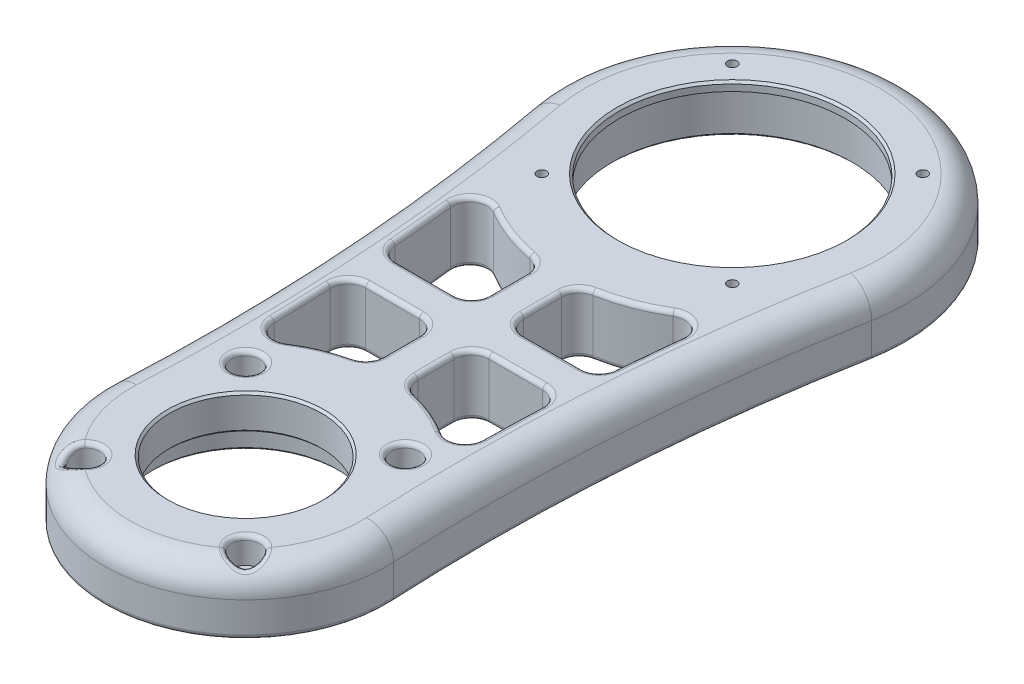
SolidWorks part; units mm, degrees
ref_plane "Front" through (0, 0, 0) normal (0, 0, 1) x (1, 0, 0)
ref_plane "Top" through (0, 0, 0) normal (0, 1, 0) x (1, 0, 0)
ref_plane "Right" through (0, 0, 0) normal (1, 0, 0) x (0, 0, -1)
sketch "Эскиз1" plane through (0, 0, 0) normal (0, 1, 0) x (1, 0, 0)
  line L0 (0, 0) -> (0, 112) construction
  line L3 (0, 0) -> (0, -109) construction
  circle A0 centre (0, 112) radius 40
  circle A1 centre (0, 0) radius 32.5
  circle A2 centre (0, -109) radius 50
  arc A3 (-48.1763, -95.6191) -> (-39.3342, 104.7321) centre (-477.8164, 23.7129) ccw
  arc A4 (39.3342, 104.7321) -> (48.1763, -95.6191) centre (477.8164, 23.7129) ccw
  dimension "D2" = 80
  dimension "D3" = 65
  dimension "D5" = 100
  dimension "D1" = 112
  dimension "D4" = 109
extrude "Бобышка-Вытянуть1" add sketch "Эскиз1" along normal blind 14 contours A2 A1 | A1 A0 | A0 region at (0, 0, -112) region at (0, 0, -52.811) region at (0, 0, 0)
sketch "Эскиз2" plane through (0, 0, 0) normal (0, 1, 0) x (1, 0, 0)
  circle A0 centre (0, 0) radius 21.1
  dimension "D1" = 42.2
extrude "Вырез-Вытянуть2" cut sketch "Эскиз2" along normal blind 6
sketch "Эскиз3" plane through (0, 0, 0) normal (0, 1, 0) x (1, 0, 0)
  circle A0 centre (0, 0) radius 17.5
  dimension "D1" = 35
extrude "Вырез-Вытянуть4" cut sketch "Эскиз3" along normal through all
sketch "Эскиз4" plane through (0, 0, 0) normal (0, 1, 0) x (1, 0, 0)
  line L0 (0, 0) -> (0, 65.2467) construction
  line L1 (0, 0) -> (-110.2485, 0) construction
  line L2 (0, 0) -> (18.3848, 18.3848) construction
  circle A0 centre (0, 0) radius 26 construction
  circle A1 centre (18.3848, 18.3848) radius 1.75
  circle A2 centre (18.3848, -18.3848) radius 1.75
  circle A3 centre (-18.3848, -18.3848) radius 1.75
  circle A4 centre (-18.3848, 18.3848) radius 1.75
  point P18 (0, 0)
  dimension "D1" = 45
  dimension "D2" = 3.5
  dimension "D3" = 52
extrude "Вырез-Вытянуть6" cut sketch "Эскиз4" along normal through all
sketch "Эскиз5" plane through (0, 0, 0) normal (0, 1, 0) x (1, 0, 0)
  circle A7 centre (0, 0) radius 26 construction
  circle A8 centre (18.3848, 18.3848) radius 3.25
  circle A9 centre (18.3848, -18.3848) radius 3.25
  circle A10 centre (-18.3848, -18.3848) radius 3.25
  circle A11 centre (-18.3848, 18.3848) radius 3.25
  point P14 (0, 0)
  dimension "D1" = 6.5
  dimension "D2" = 52
  dimension "D3" = 4
extrude "Вырез-Вытянуть7" cut sketch "Эскиз5" along normal through all from offset 8 contours A7 | A10 | A11 | A8 | A9 region at (18.3848, 0, -18.3848) region at (18.3848, 0, 18.3848) region at (-18.3848, 0, 18.3848) region at (-18.3848, 0, -18.3848)
sketch "Эскиз6" plane through (0, 0, 0) normal (0, 1, 0) x (1, 0, 0)
  line L0 (0, 0) -> (0, 112) construction
  circle A1 centre (0, 112) radius 26
  circle A2 centre (0, 112) radius 27.6
  circle A3 centre (0, 112) radius 35.5
  dimension "D1" = 52
  dimension "D2" = 71
  dimension "D3" = 55.2
extrude "Вырез-Вытянуть8" cut sketch "Эскиз6" along normal through all contours A1 region at (0, 0, -112)
extrude "Вырез-Вытянуть9" cut sketch "Эскиз6<4>" along normal blind 2 contours A3
sketch "Эскиз6<4>" plane through (0, 0, 0) normal (0, 1, 0) x (1, 0, 0) same geometry as "Эскиз6"
extrude "Вырез-Вытянуть10" cut sketch "Эскиз6<5>" along normal blind 12 contours A2
sketch "Эскиз6<5>" plane through (0, 0, 0) normal (0, 1, 0) x (1, 0, 0) same geometry as "Эскиз6"
fillet "Скругление1" radius 1 4 edges at (0, 0, -152) (-32.8994, 0, -53.3714) (0, 0, 32.5) (32.8994, 0, -53.3714)
fillet "Скругление2" radius 6 4 edges at (0, 14, -152) (-32.8994, 14, -53.3714) (0, 14, 32.5) (32.8994, 14, -53.3714)
chamfer "Фаска1" distance 0.5 angle 45 5 edges at (0, 14, 17.5) (0, 6, 17.5) (0, 0, 21.1) (0, 2, -84.4) (0, 14, -86)
fillet "Скругление3" radius 1 6 edges at (20.276, 13.3526, 21.0279) (-21.0279, 13.3526, 20.276) (16.0867, 14, 16.0867) (-16.0867, 14, 16.0867) (-18.3848, 14, -15.1348) (18.3848, 14, -15.1348)
sketch "Эскиз8" plane through (0, 0, 0) normal (0, 1, 0) x (1, 0, 0)
  line L0 (0, 112) -> (21.9203, 133.9203) construction
  line L1 (0, 112) -> (21.9203, 90.0797) construction
  line L2 (0, 112) -> (-21.9203, 90.0797) construction
  line L3 (0, 112) -> (-21.9203, 133.9203) construction
  circle A0 centre (0, 112) radius 31 construction
  circle A1 centre (21.9203, 133.9203) radius 1.1
  circle A2 centre (21.9203, 90.0797) radius 1.1
  circle A3 centre (-21.9203, 90.0797) radius 1.1
  circle A4 centre (-21.9203, 133.9203) radius 1.1
  point P14 (0, 112)
  dimension "D1" = 62
  dimension "D2" = 2.2
  dimension "D3" = 4
extrude "Вырез-Вытянуть11" cut sketch "Эскиз8" along normal through all
sketch "Эскиз9" plane through (0, 0, 0) normal (0, 1, 0) x (1, 0, 0)
  line L0 (0, 112) -> (21.9203, 90.0797) construction
  line L1 (20.2057, 88.365) -> (22.5479, 87.7374)
  line L2 (22.5479, 87.7374) -> (24.2626, 89.4521)
  line L3 (24.2626, 89.4521) -> (23.635, 91.7943)
  line L4 (23.635, 91.7943) -> (21.2927, 92.4219)
  line L5 (21.2927, 92.4219) -> (19.5781, 90.7073)
  line L6 (19.5781, 90.7073) -> (20.2057, 88.365)
  line L7 (0, 112) -> (-21.9203, 90.0797) construction
  line L8 (-23.635, 91.7943) -> (-24.2626, 89.4521)
  line L9 (-24.2626, 89.4521) -> (-22.5479, 87.7374)
  line L10 (-22.5479, 87.7374) -> (-20.2057, 88.365)
  line L11 (-20.2057, 88.365) -> (-19.5781, 90.7073)
  line L12 (-19.5781, 90.7073) -> (-21.2927, 92.4219)
  line L13 (-21.2927, 92.4219) -> (-23.635, 91.7943)
  line L14 (0, 112) -> (-21.9203, 133.9203) construction
  line L15 (-20.2057, 135.635) -> (-22.5479, 136.2626)
  line L16 (-22.5479, 136.2626) -> (-24.2626, 134.5479)
  line L17 (-24.2626, 134.5479) -> (-23.635, 132.2057)
  line L18 (-23.635, 132.2057) -> (-21.2927, 131.5781)
  line L19 (-21.2927, 131.5781) -> (-19.5781, 133.2927)
  line L20 (-19.5781, 133.2927) -> (-20.2057, 135.635)
  line L21 (0, 112) -> (21.9203, 133.9203) construction
  line L22 (23.635, 132.2057) -> (24.2626, 134.5479)
  line L23 (24.2626, 134.5479) -> (22.5479, 136.2626)
  line L24 (22.5479, 136.2626) -> (20.2057, 135.635)
  line L25 (20.2057, 135.635) -> (19.5781, 133.2927)
  line L26 (19.5781, 133.2927) -> (21.2927, 131.5781)
  line L27 (21.2927, 131.5781) -> (23.635, 132.2057)
  circle A0 centre (21.9203, 90.0797) radius 2.1 construction
  circle A1 centre (-21.9203, 90.0797) radius 2.1 construction
  circle A2 centre (-21.9203, 133.9203) radius 2.1 construction
  circle A3 centre (21.9203, 133.9203) radius 2.1 construction
  point P38 (0, 112)
  dimension "D1" = 4.2
  dimension "D2" = 4
extrude "Вырез-Вытянуть13" cut sketch "Эскиз9" along normal blind 11
sketch "Эскиз10" plane through (0, 0, 0) normal (0, 1, 0) x (1, 0, 0)
  line L0 (0, 0) -> (0, 112) construction
  line L1 (0, 0) -> (0, -109) construction
  line L2 (4, 0) -> (4, 112)
  line L3 (-4, 0) -> (-4, 112)
  line L4 (-49.8114, 52) -> (68.764, 52)
  line L5 (-49.8114, 48) -> (68.764, 48)
  line L6 (-49.8114, 56) -> (68.764, 56)
  circle A0 centre (0, 112) radius 40
  circle A1 centre (0, 0) radius 32.5
  circle A2 centre (0, -109) radius 50
  arc A3 (-48.1763, -95.6191) -> (-39.3342, 104.7321) centre (-477.8164, 23.7129) ccw
  arc A4 (39.3342, 104.7321) -> (48.1763, -95.6191) centre (477.8164, 23.7129) ccw
  arc A5 (-40.4681, -97.7601) -> (-31.4673, 106.1857) centre (-477.8164, 23.7129) ccw
  arc A6 (31.4673, 106.1857) -> (40.4681, -97.7601) centre (477.8164, 23.7129) ccw
  dimension "D2" = 80
  dimension "D3" = 65
  dimension "D5" = 100
  dimension "D1" = 112
  dimension "D4" = 109
  dimension "D6" = 52
extrude "Вырез-Вытянуть15" cut sketch "Эскиз10" along normal through all contours A5 A1 L3 L5 | A5 L6 L3 A0 | A6 A0 L2 L6 | A6 L5 L2 A1 region at (14.9305, 0, -38.1453) region at (-14.9305, 0, -38.1453) region at (16.0421, 0, -66.3771) region at (-16.0421, 0, -66.3771)
fillet "Скругление4" radius 4 16 edges at (4, 7, -32.2529) (4, 7, -48) (23.9152, 7, -22.0072) (24.5622, 7, -48) (-4, 7, -48) (-24.5622, 7, -48) (-23.9152, 7, -22.0072) (-4, 7, -32.2529) (-25.0617, 7, -56) (4, 7, -72.2005) (4, 7, -56) (-4, 7, -56) (25.0617, 7, -56) (27.8369, 7, -83.2753) (-4, 7, -72.2005) (-27.8369, 7, -83.2753)
fillet "Скругление5" radius 1 1 edges at (0, 0, -76.5)
fillet "Скругление6" radius 1 64 edges at (-5.1716, 14, -46.8284) (-4, 14, -39.8062) (-4.877, 14, -33.1132) (-12.6512, 14, -29.9366) (-21.8406, 14, -27.0249) (-24.1112, 14, -37.1614) (-23.252, 14, -46.7651) (21.8406, 14, -27.0249) (12.6512, 14, -29.9366) (4.877, 14, -33.1132) (4, 14, -39.8062) (5.1716, 14, -46.8284) (14.1808, 14, -48) (23.252, 14, -46.7651) (-4.9252, 14, -71.2918) (-14.1911, 14, -74.602) (-24.8737, 14, -77.6865) (-25.9602, 14, -66.7847) (-24.0661, 14, -57.0616) (-14.676, 14, -56) (-5.1716, 14, -57.1716) (24.0661, 14, -57.0616) (14.676, 14, -56) (5.1716, 14, -57.1716) (4, 14, -64.3667) (4.9252, 14, -71.2918) (14.1911, 14, -74.602) (24.8737, 14, -77.6865) (-5.1716, 0, -57.1716) (-14.676, 0, -56) (-24.0661, 0, -57.0616) (-25.9602, 0, -66.7847) (-24.8737, 0, -77.6865) (-14.1911, 0, -74.602) (-4.9252, 0, -71.2918) (-4.877, 0, -33.1132) (-12.6512, 0, -29.9366) (-21.8406, 0, -27.0249) (-24.1112, 0, -37.1614) (-23.252, 0, -46.7651) (-14.1808, 0, -48) (-5.1716, 0, -46.8284) (4.877, 0, -33.1132) (12.6512, 0, -29.9366) (21.8406, 0, -27.0249) (24.1112, 0, -37.1614) (23.252, 0, -46.7651) (14.1808, 0, -48) (5.1716, 0, -46.8284) (5.1716, 0, -57.1716) (14.676, 0, -56) (24.0661, 0, -57.0616) (25.9602, 0, -66.7847) (24.8737, 0, -77.6865) (14.1911, 0, -74.602) (4.9252, 0, -71.2918) (-14.1808, 14, -48) (24.1112, 14, -37.1614) (-4, 14, -64.3667) (25.9602, 14, -66.7847) (-4, 0, -64.3667) (-4, 0, -39.8062) (4, 0, -39.8062) (4, 0, -64.3667)
